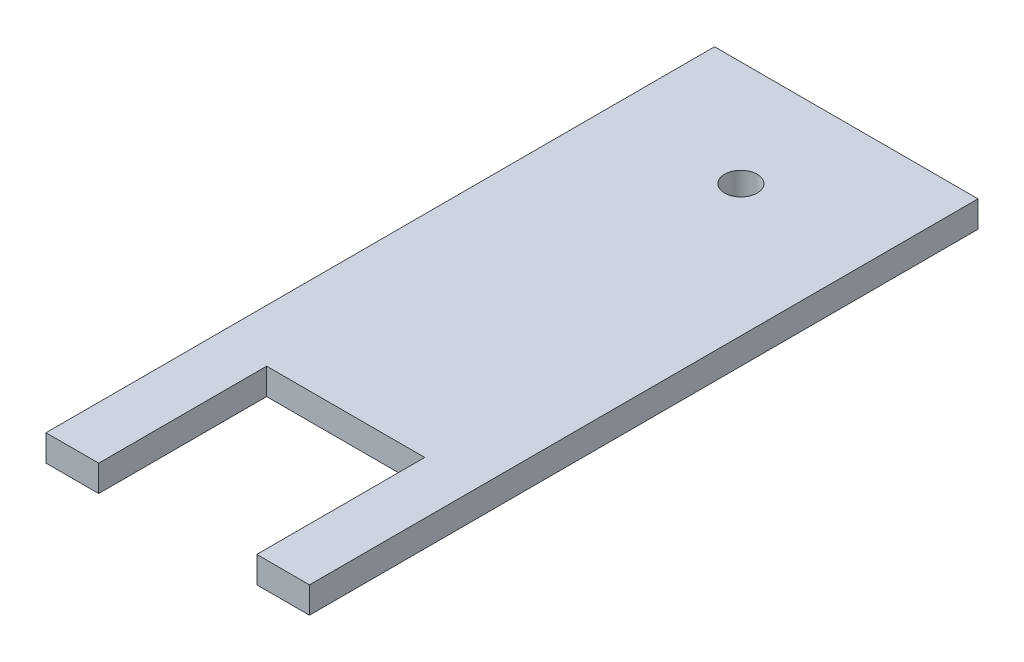
SolidWorks part; units mm, degrees
material "Maple"
ref_plane "Front Plane" through (0, 0, 0) normal (0, 0, 1) x (1, 0, 0)
ref_plane "Top Plane" through (0, 0, 0) normal (0, 1, 0) x (1, 0, 0)
ref_plane "Right Plane" through (0, 0, 0) normal (1, 0, 0) x (0, 0, -1)
sketch "Sketch1" plane through (0, 0, 0) normal (0, 1, 0) x (1, 0, 0)
  line L0 (0, 0) -> (127, 0)
  line L1 (0, 0) -> (0, 241.3)
  line L2 (127, 0) -> (127, 241.3)
  line L3 (0, 241.3) -> (127, 241.3)
  line L4 (63.5, 241.3) -> (63.5, 0) construction
  line L5 (127, 0) -> (101.6, 0)
  line L6 (127, 0) -> (127, -80.9625)
  line L7 (101.6, 0) -> (101.6, -80.9625)
  line L8 (127, -80.9625) -> (101.6, -80.9625)
  line L9 (25.4, 0) -> (0, 0)
  line L10 (25.4, 0) -> (25.4, -80.9625)
  line L11 (0, 0) -> (0, -80.9625)
  line L12 (25.4, -80.9625) -> (0, -80.9625)
  circle A0 centre (63.5, 190.5) radius 7.874
  dimension "D3" = 15.748
  dimension "D4" = 50.8
  dimension "D1" = 127
  dimension "D2" = 241.3
  dimension "D5" = 76.2
  dimension "D6" = 25.4
  dimension "D7" = 80.9625
extrude "Boss-Extrude1" add sketch "Sketch1" along normal blind 12.7 contours L3 L4 A0 L0 L2 | L4 L3 L1 L0 A0 | L8 L6 L0 L7 | L12 L10 L0 L11 region at (31.5683, 0, -120.2032) region at (12.7, 0, 40.4813) region at (95.4317, 0, -120.2032) region at (114.3, 0, 40.4812)
ref_plane "Plane1" through (63.5, 0, 0) normal (-1, 0, 0) x (0, 0, 1)
